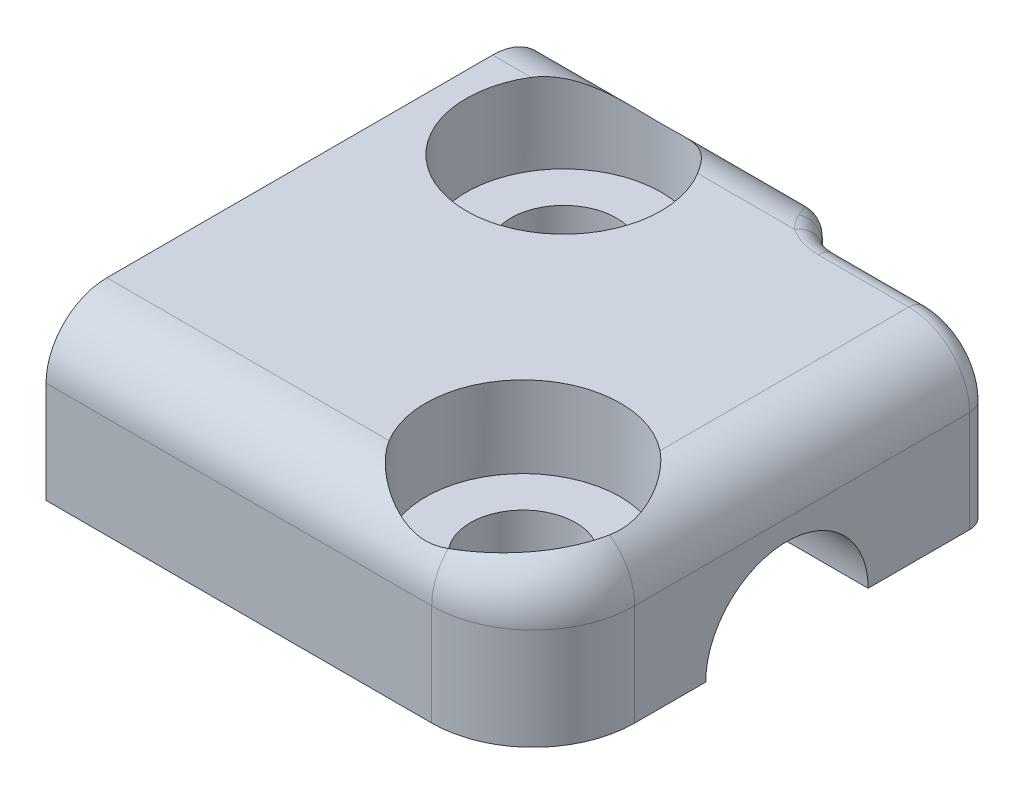
SolidWorks part; units mm, degrees
ref_plane "Front Plane" through (0, 0, 0) normal (0, 0, 1) x (1, 0, 0)
ref_plane "Top Plane" through (0, 0, 0) normal (0, 1, 0) x (1, 0, 0)
ref_plane "Right Plane" through (0, 0, 0) normal (1, 0, 0) x (0, 0, -1)
sketch "Sketch1" plane through (0, 0, 0) normal (0, 1, 0) x (1, 0, 0)
  line L1 (-12, 12.5) -> (12, 12.5)
  line L2 (-12, 12.5) -> (-12, -12.5)
  line L3 (-12, -12.5) -> (12, -12.5)
  line L4 (12, 12.5) -> (12, -12.5)
  line L5 (-12, 12.5) -> (12, -12.5) construction
  line L6 (-12, -12.5) -> (12, 12.5) construction
  point P0 (0, 0)
  dimension "D1" = 25
  dimension "D2" = 24
extrude "Boss-Extrude1" add sketch "Sketch1" along normal blind 8
sketch "Sketch2" plane through (-12, 0, 0) normal (-1, 0, 0) x (0, 0, 1)
  circle A0 centre (0, 0) radius 4
  dimension "D1" = 8
extrude "Cut-Extrude1" cut sketch "Sketch2" against normal through all
sketch "Sketch3" plane through (0, 0, 0) normal (0, -1, 0) x (1, 0, 0)
  line L0 (-6, -7) -> (6, 7) construction
  line L1 (-6, -7) -> (12.0808, -7) construction
  circle A0 centre (-6, -7) radius 2.6
  circle A1 centre (6, 7) radius 2.6
extrude "Cut-Extrude2" cut sketch "Sketch3" against normal through all
sketch "Sketch6" plane through (0, 0, -12.5) normal (0, 0, -1) x (-1, 0, 0)
  line L0 (-12, 0) -> (12, 0) construction
  line L1 (-12, 8) -> (-3.5, 8)
  line L2 (-12, 8) -> (-12, 0)
  line L3 (-12, 0) -> (-3.5, 0)
  line L4 (-3.5, 8) -> (-3.5, 0)
  dimension "D1" = 8.5
extrude "Cut-Extrude4" cut sketch "Sketch6" against normal blind 2.5
fillet "Fillet1" radius 3 3 edges at (-4.25, 8, -12.5) (12, 8, 1.25) (0, 8, 12.5)
fillet "Fillet2" radius 5 3 edges at (11.1213, 7.1213, 11.6213) (12, 2.5, 12.5) (3.5, 2.5, -12.5)
sketch "Sketch4" plane through (0, 8, 0) normal (0, 1, 0) x (-1, 0, 0)
  circle A0 centre (6, -7) radius 4.8
  circle A1 centre (-6, 7) radius 4.8
  circle A2 centre (-6, 7) radius 2.6 construction
  circle A3 centre (6, -7) radius 2.6 construction
  dimension "D1" = 9.6
extrude "Cut-Extrude3" cut sketch "Sketch4" against normal blind 4
fillet "Fillet4" radius 2 1 edges at (3.5, 3.979, -10)
fillet "Fillet3" radius 1 5 edges at (11.2913, 6.9365, -10) (12, 2.5, -10) (7.0159, 7.958, -10) (3.8868, 7.938, -10.1069) (1.2789, 6.6068, -12.0334)
